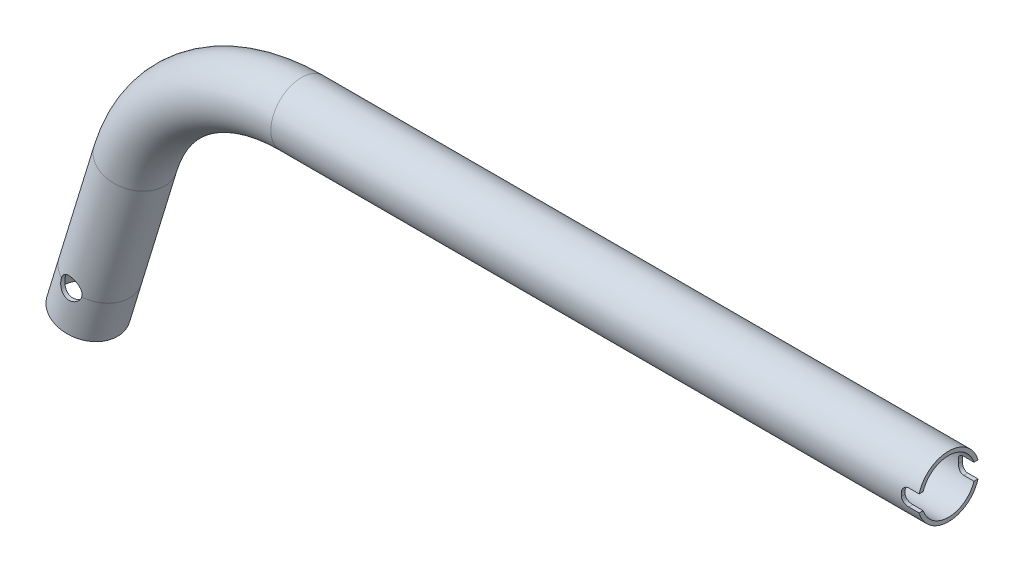
SolidWorks part; units mm, degrees
ref_plane "Front Plane" through (0, 0, 0) normal (0, 0, 1) x (1, 0, 0)
ref_plane "Top Plane" through (0, 0, 0) normal (0, 1, 0) x (1, 0, 0)
ref_plane "Right Plane" through (0, 0, 0) normal (1, 0, 0) x (0, 0, -1)
sketch "Sketch1" plane through (0, 0, 0) normal (0, 0, 1) x (1, 0, 0)
  line L0 (-92.2396, 0) -> (92.2396, 0)
  line L1 (-143.88, -38.2119) -> (-154.7604, -73.8)
  line L2 (92.2396, 0) -> (108.8396, 0)
  line L3 (-154.7604, -73.8) -> (-158.4903, -86)
  arc A0 (-92.2396, 0) -> (-143.88, -38.2119) centre (-92.2396, -54) ccw
  point P4 (0, 0)
  point P10 (-154.7604, -73.8)
  dimension "D2" = 54
  dimension "D1" = 73
  dimension "D3" = 73.8
  dimension "D4" = 247
  dimension "D5" = 86
  dimension "D6" = 73
  dimension "D7" = 16.6
ref_plane "Plane1" through (92.2396, 0, 0) normal (1, 0, 0) x (0, 0, -1)
sketch "Sketch3" plane through (92.2396, 0, 0) normal (1, 0, 0) x (0, 0, -1)
  circle A0 centre (0, 0) radius 9.5
  circle A1 centre (0, 0) radius 8.3
  dimension "D1" = 1.2
  dimension "D2" = 19
sweep "Sweep2" add profiles "Sketch3" path "Sketch1"
ref_axis "Axis1" through (108.8396, 0, 0) along (-1, 0, 0)
ref_axis "Axis2" through (-142.3269, -33.1317, 0) along (-0.2924, -0.9563, 0)
sketch "Sketch4" plane through (0, 0, 0) normal (0, 0, 1) x (1, 0, 0)
  line L0 (-163.8453, -71.0225) -> (-145.6755, -76.5775) construction
  line L1 (92.2396, -101.4635) -> (92.2396, 101.4635) construction
  line L2 (108.8396, 0) -> (92.2396, 0) construction
  line L3 (108.8396, -9.5) -> (108.8396, 9.5) construction
  line L4 (108.8396, 0) -> (-92.2396, 0) construction
  line L5 (108.8396, 2.5555) -> (108.8396, -2.5555)
  line L6 (90.2396, -5.5) -> (94.2396, -5.5)
  line L7 (88.2396, -3.5) -> (88.2396, 3.5)
  line L8 (90.2396, 5.5) -> (94.2396, 5.5)
  line L9 (96.2396, -3.5) -> (96.2396, 3.5)
  line L10 (88.2396, -5.5) -> (96.2396, 5.5) construction
  line L11 (88.2396, 5.5) -> (96.2396, -5.5) construction
  line L12 (105.6396, -2.5555) -> (108.8396, -2.5555)
  line L13 (103.6396, -0.5555) -> (103.6396, 0.5555)
  line L14 (105.6396, 2.5555) -> (108.8396, 2.5555)
  line L16 (103.6396, -2.5555) -> (108.8396, 0) construction
  line L17 (103.6396, 2.5555) -> (108.8396, 0) construction
  circle A0 centre (-154.7604, -73.8) radius 3.3
  arc A1 (90.2396, -5.5) -> (88.2396, -3.5) centre (90.2396, -3.5) cw
  arc A2 (96.2396, -3.5) -> (94.2396, -5.5) centre (94.2396, -3.5) cw
  arc A3 (94.2396, 5.5) -> (96.2396, 3.5) centre (94.2396, 3.5) cw
  arc A4 (90.2396, 5.5) -> (88.2396, 3.5) centre (90.2396, 3.5) ccw
  arc A5 (105.6396, -2.5555) -> (103.6396, -0.5555) centre (105.6396, -0.5555) cw
  arc A6 (103.6396, 0.5555) -> (105.6396, 2.5555) centre (105.6396, 0.5555) cw
  dimension "D1" = 16.6
  dimension "D4" = 2
  dimension "D5" = 2
  dimension "D2" = 8
  dimension "D3" = 11
extrude "Cut-Extrude1" cut sketch "Sketch4" against normal up to next
sketch "Sketch5" plane through (0, 0, 0) normal (0, 0, 1) x (1, 0, 0)
  circle A0 centre (-154.7604, -73.8) radius 3.3
extrude "Cut-Extrude2" cut sketch "Sketch5" along normal through all
sketch "Sketch6" plane through (0, 0, 0) normal (0, 0, 1) x (1, 0, 0)
  line L1 (108.8396, 2.5555) -> (105.6396, 2.5555)
  line L2 (108.8396, 2.5555) -> (108.8396, -2.5555)
  line L3 (108.8396, -2.5555) -> (105.6396, -2.5555)
  line L4 (103.6396, 0.5555) -> (103.6396, -0.5555)
  arc A0 (103.6396, -0.5555) -> (105.6396, -2.5555) centre (105.6396, -0.5555) ccw
  arc A1 (103.6396, 0.5555) -> (105.6396, 2.5555) centre (105.6396, 0.5555) cw
  dimension "D1" = 2
extrude "Cut-Extrude3" cut sketch "Sketch6" along normal blind 10
